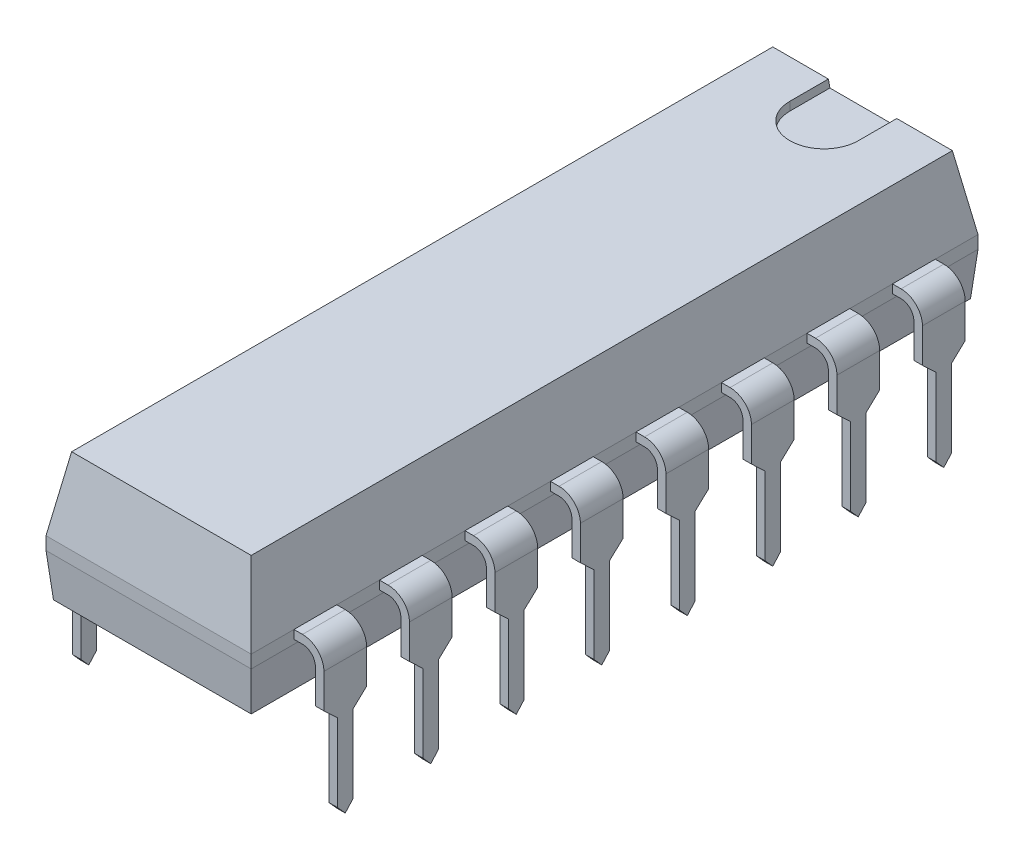
SolidWorks part; units mm, degrees
ref_plane "x/y" through (0, 0, 0) normal (0, 0, 1) x (1, 0, 0)
ref_plane "x/z" through (0, 0, 0) normal (0, 1, 0) x (1, 0, 0)
ref_plane "y/z" through (0, 0, 0) normal (1, 0, 0) x (0, 0, -1)
ref_plane "Plane1" through (0, 0.381, 0) normal (0, 1, 0) x (-1, 0, 0)
sketch "Sketch1" plane through (0, 0.381, 0) normal (0, 1, 0) x (0, 0, -1)
  line L1 (1.905, -0.762) -> (-19.685, -0.762)
  line L2 (1.905, -0.762) -> (1.905, -6.858)
  line L3 (1.905, -6.858) -> (-19.685, -6.858)
  line L4 (-19.685, -0.762) -> (-19.685, -6.858)
  dimension "D1" = 19.685
  dimension "D2" = 1.905
  dimension "D3" = 6.096
  dimension "D4" = 0.762
extrude "Base-Extrude" add sketch "Sketch1" along normal blind 3.81
ref_plane "Plane2" through (6.858, 0, 0) normal (1, 0, 0) x (0, 0, -1)
ref_plane "Plane5" through (0, 0, 19.685) normal (0, 0, 1) x (1, 0, 0)
chamfer "Chamfer1" distance 2.159 angle 10 4 edges at (6.858, 4.191, 8.89) (3.81, 4.191, 19.685) (0.762, 4.191, 8.89) (3.81, 4.191, -1.905) first distance on face at (6.858, 2.286, 8.89) first distance on face at (3.81, 2.286, 19.685) first distance on face at (0.762, 2.286, 8.89) first distance on face at (3.81, 2.286, -1.905)
chamfer "Chamfer2" distance 1.27 angle 5 4 edges at (0.762, 0.381, 8.89) (3.81, 0.381, 19.685) (6.858, 0.381, 8.89) (3.81, 0.381, -1.905) first distance on face at (0.762, 1.2065, 8.89) first distance on face at (3.81, 1.2065, 19.685) first distance on face at (6.858, 1.2065, 8.89) first distance on face at (3.81, 1.2065, -1.905)
sketch "Sketch2" plane through (0, 4.191, 0) normal (0, 1, 0) x (-1, 0, 0)
  line L5 (-3.81, -1.905) -> (-3.81, 2.9023) construction
  line L6 (-0.762, -1.905) -> (-6.858, -1.905) construction
  line L8 (-2.794, -1.905) -> (-4.826, -1.905)
  line L9 (-2.794, -1.905) -> (-2.794, -0.381)
  line L11 (-4.826, -1.905) -> (-4.826, -0.381)
  arc A1 (-2.794, -0.381) -> (-4.826, -0.381) centre (-3.81, -0.381) ccw
  dimension "D2" = 2.032
  dimension "D3" = 1.016
  dimension "D1" = 1.016
  dimension "D4" = 1.524
extrude "Cut-Extrude1" cut sketch "Sketch2" against normal blind 0.254
ref_plane "Plane6" through (8.763, 0, 0) normal (1, 0, 0) x (0, 0, -1)
sketch "Sketch3" plane through (9.017, 0, 0) normal (0, 0, -1) x (-1, 0, 0)
  line L0 (9.017, 1.397) -> (9.017, -2.5654)
  line L1 (8.509, 1.905) -> (6.0946, 1.905)
  line L3 (8.1439, 0.381) -> (2.2701, 0.381) construction
  arc A0 (8.509, 1.905) -> (9.017, 1.397) centre (8.509, 1.397) cw
  dimension "D2" = 0.508
  dimension "D1" = 1.524
extrude "Boss-Extrude-Thin1" add sketch "Sketch3" along normal mid plane 1.27 thin thin type mid plane wall 0.254
sketch "Sketch4" plane through (0.127, 0, 0) normal (1, 0, 0) x (0, 0, -1)
  line L0 (-0.635, 0.381) -> (-0.2286, 0)
  line L1 (-0.2286, 0) -> (-0.2286, -2.3095)
  line L2 (-0.2286, -2.3095) -> (0, -2.5654)
  line L3 (0, 0) -> (0, -2.9486) construction
  line L4 (0.635, -2.5654) -> (-0.635, -2.5654) construction
  line L5 (-0.635, -2.5654) -> (-0.635, 1.397) construction
  line L6 (0, -2.5654) -> (-0.635, -2.5654)
  line L7 (-0.635, -2.5654) -> (-0.635, 0.381)
  dimension "D1" = 2.9464
  dimension "D2" = 0.4064
extrude "Cut-Extrude2" cut sketch "Sketch4" against normal up to vertex (0.254 mm away) up to point (-0.127, 1.397, 0.635)
sketch "Sketch5" plane through (0.127, 0, 0) normal (1, 0, 0) x (0, 0, -1)
  line L0 (0.635, -2.5654) -> (0, -2.5654) construction
  line L1 (0.635, -2.5654) -> (0, -2.5654)
  line L2 (0.635, -2.5654) -> (0.635, 0.381)
  line L3 (0.635, 0.381) -> (0.2286, 0)
  line L4 (0.635, -2.5654) -> (0.635, 1.397) construction
  line L5 (0.2286, 0) -> (0.2286, -2.3095)
  line L6 (0.2286, -2.3095) -> (0, -2.5654)
  line L7 (0, -2.5654) -> (-0.2286, -2.3095) construction
  line L8 (-0.2286, 0) -> (-0.635, 0.381) construction
extrude "Cut-Extrude3" cut sketch "Sketch5" against normal up to vertex (0.254 mm away) up to point (-0.127, 1.397, -0.635)
ref_plane "Plane7" through (3.81, 0, 0) normal (1, 0, 0) x (0, 0, -1)
pattern_linear "LPattern1" count 8 spacing 2.54 along (0, 0, 1) of "Cut-Extrude2", "Cut-Extrude3", "Boss-Extrude-Thin1"
mirror "Mirror1" about plane through (3.81, 0, 0) normal (1, 0, 0) of "LPattern1"
sketch "CW" plane through (0, 0.381, 0) normal (0, -1, 0) x (1, 0, 0)
  line L6 (6.7469, 19.5739) -> (0.8731, 19.5739)
  line L7 (0.8731, 19.5739) -> (0.8731, -1.7939)
  line L8 (0.8731, -1.7939) -> (6.7469, -1.7939)
  line L9 (6.7469, -1.7939) -> (6.7469, 19.5739)
  line L10 (6.7469, 19.5739) -> (0.8731, 19.5739)
  line L11 (0.8731, 19.5739) -> (0.8731, -1.7939)
  line L13 (0.8731, -1.7939) -> (6.7469, -1.7939)
  line L29 (6.7469, -1.7939) -> (6.7469, 19.5739)
  dimension "D1" = 0
ref_axis "Y" through (80.9, 0, 0) along (-1, 0, 0)
ref_axis "X" through (0, 0, 50) along (0, 0, -1)
ref_axis "Z" through (0, -50, 0) along (0, 1, 0)
sketch "Component_Outline" plane through (0, 0, 0) normal (0, 1, 0) x (1, 0, 0)
  line L0 (6.858, 1.905) -> (6.858, 0.635)
  line L1 (6.858, 0.635) -> (7.747, 0.635)
  line L2 (7.747, 0.635) -> (7.747, -0.635)
  line L3 (7.747, -0.635) -> (6.858, -0.635)
  line L4 (6.858, -0.635) -> (6.858, -1.905)
  line L5 (6.858, -1.905) -> (7.747, -1.905)
  line L6 (7.747, -1.905) -> (7.747, -3.175)
  line L7 (7.747, -3.175) -> (6.858, -3.175)
  line L8 (6.858, -3.175) -> (6.858, -4.445)
  line L9 (6.858, -4.445) -> (7.747, -4.445)
  line L10 (7.747, -4.445) -> (7.747, -5.715)
  line L11 (7.747, -5.715) -> (6.858, -5.715)
  line L12 (6.858, -5.715) -> (6.858, -6.985)
  line L13 (6.858, -6.985) -> (7.747, -6.985)
  line L14 (7.747, -6.985) -> (7.747, -8.255)
  line L15 (7.747, -8.255) -> (6.858, -8.255)
  line L16 (6.858, -8.255) -> (6.858, -9.525)
  line L17 (6.858, -9.525) -> (7.747, -9.525)
  line L18 (7.747, -9.525) -> (7.747, -10.795)
  line L19 (7.747, -10.795) -> (6.858, -10.795)
  line L20 (6.858, -10.795) -> (6.858, -12.065)
  line L21 (6.858, -12.065) -> (7.747, -12.065)
  line L22 (7.747, -12.065) -> (7.747, -13.335)
  line L23 (7.747, -13.335) -> (6.858, -13.335)
  line L24 (6.858, -13.335) -> (6.858, -14.605)
  line L25 (6.858, -14.605) -> (7.747, -14.605)
  line L26 (7.747, -14.605) -> (7.747, -15.875)
  line L27 (7.747, -15.875) -> (6.858, -15.875)
  line L28 (6.858, -15.875) -> (6.858, -17.145)
  line L29 (6.858, -17.145) -> (7.747, -17.145)
  line L30 (7.747, -17.145) -> (7.747, -18.415)
  line L31 (7.747, -18.415) -> (6.858, -18.415)
  line L32 (6.858, -18.415) -> (6.858, -19.685)
  line L33 (3.81, -19.5739) -> (3.81, 1.7939) construction
  line L34 (6.7469, -19.5739) -> (0.8731, -19.5739) construction
  line L35 (0.8731, 1.7939) -> (6.7469, 1.7939) construction
  line L36 (0.762, -18.415) -> (0.762, -19.685)
  line L37 (-0.127, -18.415) -> (0.762, -18.415)
  line L38 (-0.127, -17.145) -> (-0.127, -18.415)
  line L39 (0.762, -17.145) -> (-0.127, -17.145)
  line L40 (0.762, -15.875) -> (0.762, -17.145)
  line L41 (-0.127, -15.875) -> (0.762, -15.875)
  line L42 (-0.127, -14.605) -> (-0.127, -15.875)
  line L43 (0.762, -14.605) -> (-0.127, -14.605)
  line L44 (0.762, -13.335) -> (0.762, -14.605)
  line L45 (-0.127, -13.335) -> (0.762, -13.335)
  line L46 (-0.127, -12.065) -> (-0.127, -13.335)
  line L47 (0.762, -12.065) -> (-0.127, -12.065)
  line L48 (0.762, -10.795) -> (0.762, -12.065)
  line L49 (-0.127, -10.795) -> (0.762, -10.795)
  line L50 (-0.127, -9.525) -> (-0.127, -10.795)
  line L51 (0.762, -9.525) -> (-0.127, -9.525)
  line L52 (0.762, -8.255) -> (0.762, -9.525)
  line L53 (-0.127, -8.255) -> (0.762, -8.255)
  line L54 (-0.127, -6.985) -> (-0.127, -8.255)
  line L55 (0.762, -6.985) -> (-0.127, -6.985)
  line L56 (0.762, -5.715) -> (0.762, -6.985)
  line L57 (-0.127, -5.715) -> (0.762, -5.715)
  line L58 (-0.127, -4.445) -> (-0.127, -5.715)
  line L59 (0.762, -4.445) -> (-0.127, -4.445)
  line L60 (0.762, -3.175) -> (0.762, -4.445)
  line L61 (-0.127, -3.175) -> (0.762, -3.175)
  line L62 (-0.127, -1.905) -> (-0.127, -3.175)
  line L63 (0.762, -1.905) -> (-0.127, -1.905)
  line L64 (0.762, -0.635) -> (0.762, -1.905)
  line L65 (-0.127, -0.635) -> (0.762, -0.635)
  line L66 (-0.127, 0.635) -> (-0.127, -0.635)
  line L67 (0.762, 0.635) -> (-0.127, 0.635)
  line L68 (0.762, 1.905) -> (0.762, 0.635)
  line L69 (0.762, 1.905) -> (6.858, 1.905)
  line L70 (0.762, -19.685) -> (6.858, -19.685)
